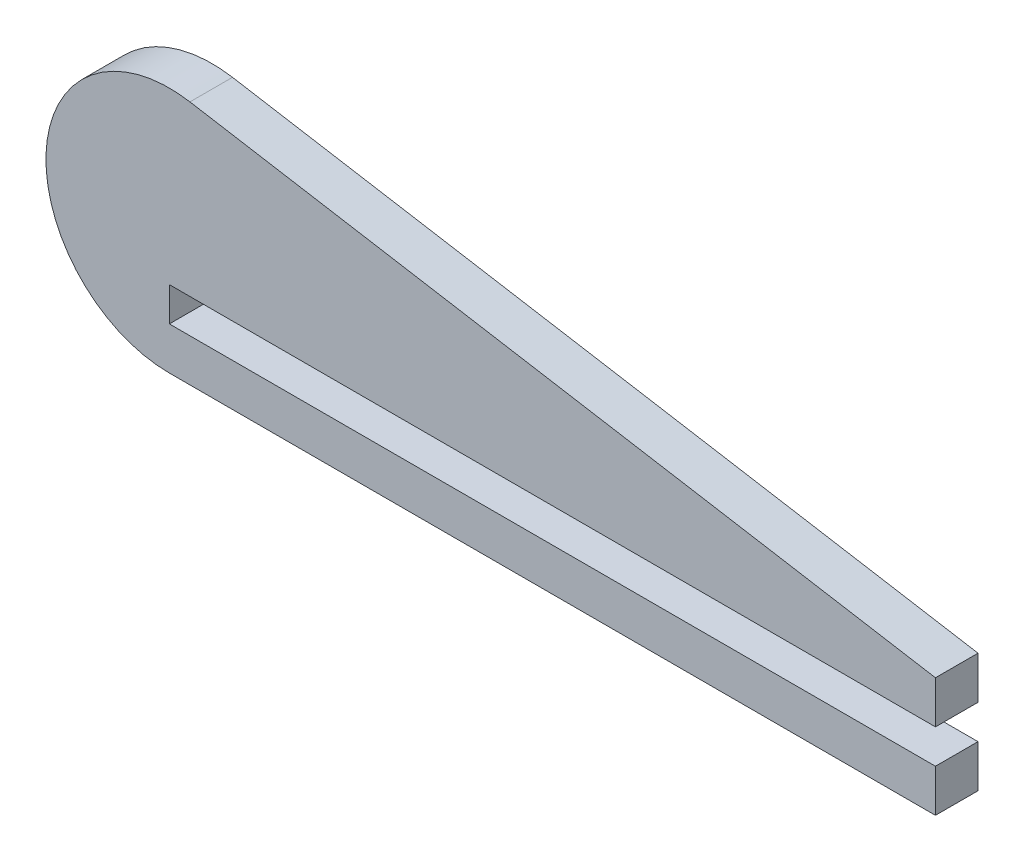
SolidWorks part; units mm, degrees
ref_plane "Alzado" through (0, 0, 0) normal (0, 0, 1) x (1, 0, 0)
ref_plane "Planta" through (0, 0, 0) normal (0, 1, 0) x (1, 0, 0)
ref_plane "Vista lateral" through (0, 0, 0) normal (1, 0, 0) x (0, 0, -1)
sketch "Croquis1" plane through (0, 0, 0) normal (0, 0, 1) x (1, 0, 0)
  line L0 (36, 0) -> (0, 0)
  line L1 (0, 0) -> (0, -1.6)
  line L2 (0, -1.6) -> (36, -1.6)
  line L3 (36, -1.6) -> (36, -3.6)
  line L4 (36, -3.6) -> (0, -3.6)
  line L5 (0.9662, 7.919) -> (36, 2)
  line L6 (36, 2) -> (36, 0)
  line L7 (-0.5276, 8) -> (-50000.5276, 8) construction
  arc A0 (0, -3.6) -> (0.9662, 7.919) centre (0, 2.2) cw
  dimension "D3" = 8
  dimension "D1" = 1.6
  dimension "D2" = 36
  dimension "D4" = 2
extrude "Saliente-Extruir1" add sketch "Croquis1" along normal blind 2
